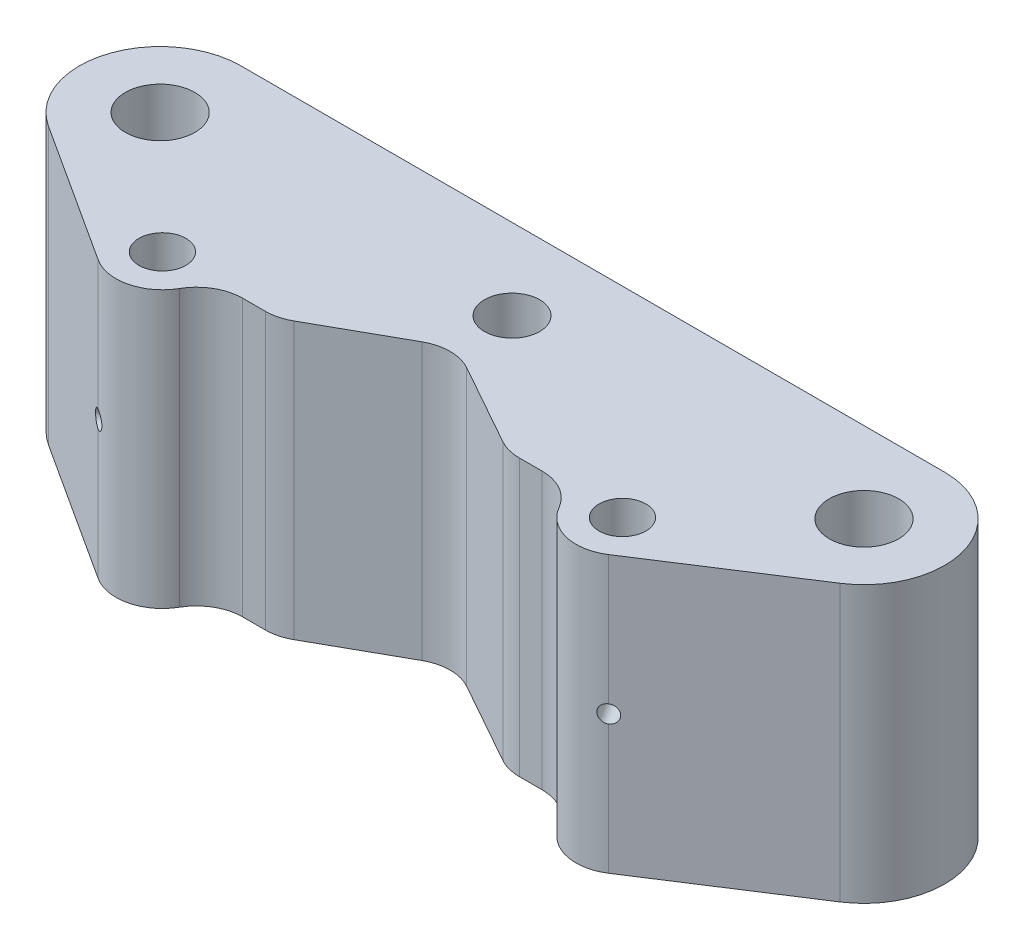
SolidWorks part; units mm, degrees
ref_plane "Płaszczyzna przednia" through (0, 0, 0) normal (0, 0, 1) x (1, 0, 0)
ref_plane "Płaszczyzna górna" through (0, 0, 0) normal (0, 1, 0) x (1, 0, 0)
ref_plane "Płaszczyzna prawa" through (0, 0, 0) normal (1, 0, 0) x (0, 0, -1)
sketch "Szkic1" plane through (0, 0, 0) normal (0, 1, 0) x (1, 0, 0)
  line L0 (-76.5, 17.55) -> (76.5, 17.55)
  line L1 (-86.027, -14.739) -> (-55.4828, -34.4823)
  line L2 (55.4828, -34.4823) -> (86.027, -14.739)
  line L3 (-50, -36.1) -> (50, -36.1)
  line L4 (-39.9, -26) -> (39.9, -26)
  circle A0 centre (-76.5, 0) radius 7.55
  circle A1 centre (76.5, 0) radius 7.55
  circle A2 centre (-76.5, 0) radius 17.55
  circle A3 centre (76.5, 0) radius 17.55
  circle A4 centre (0, 0) radius 6
  circle A5 centre (-50, -26) radius 5.1
  circle A6 centre (50, -26) radius 5.1
  circle A7 centre (-50, -26) radius 10.1
  circle A8 centre (50, -26) radius 10.1
  dimension "D1" = 15.1
  dimension "D2" = 15.1
  dimension "D7" = 12
  dimension "D8" = 10.2
  dimension "D9" = 100
  dimension "D3" = 153
  dimension "D4" = 76.5
  dimension "D10" = 50
  dimension "D11" = 26
  dimension "D5" = 10
  dimension "D6" = 10
  dimension "D12" = 5
extrude "Dodanie-wyciągnięcie1" add sketch "Szkic1" along normal blind 60 contours A2 A0 | A8 L2 A3 L0 A2 L1 A7 L3 A4 | A7 A5 | A8 A6 | A3 A1 region at (0, 0, -15.7525) region at (-64.4413, 0, -12.0587) region at (88.5587, 0, -12.0587) region at (-54.6922, 0, 17.38) region at (52.7774, 0, 35.4131)
sketch "Szkic2" plane through (0, 0, 0) normal (0, -1, 0) x (1, 0, 0)
  circle A0 centre (0, 0) radius 11
  dimension "D1" = 22
extrude "Wytnij-wyciągnięcie1" cut sketch "Szkic2" against normal blind 5
sketch "Szkic3" plane through (0, 5, 0) normal (0, -1, 0) x (1, 0, 0)
  line L0 (0, 0) -> (-5.6569, 5.6569) construction
  line L1 (0, 0) -> (0, 9.4855) construction
  circle A0 centre (0, 0) radius 8 construction
  circle A1 centre (-5.6569, 5.6569) radius 1.25
  circle A2 centre (5.6569, 5.6569) radius 1.25
  circle A3 centre (5.6569, -5.6569) radius 1.25
  circle A4 centre (-5.6569, -5.6569) radius 1.25
  point P15 (0, 0)
  dimension "D1" = 16
  dimension "D2" = 2.5
  dimension "D3" = 45
  dimension "D4" = 4
extrude "Wytnij-wyciągnięcie2" cut sketch "Szkic3" against normal blind 10
sketch "Szkic4" plane through (0, 60, 0) normal (0, 1, 0) x (1, 0, 0)
  line L0 (-25, -26) -> (0, -12)
  line L1 (-39.9, -26) -> (39.9, -26) construction
  line L2 (0, -12) -> (25, -26)
  line L3 (25, -26) -> (-25, -26)
  dimension "D1" = 14
  dimension "D2" = 50
extrude "Wytnij-wyciągnięcie3" cut sketch "Szkic4" against normal through all
fillet "Zaokrąglenie1" radius 10 5 edges at (39.9, 30, 26) (-39.9, 30, 26) (25, 30, 26) (0, 30, 12) (-25, 30, 26)
sketch "Szkic5" plane through (-32.0706, 0, 49.6155) normal (-0.5429, 0, 0.8398) x (0.8398, 0, 0.5429)
  line L0 (-22.7773, 60) -> (-32.9773, 60) construction
  line L1 (-22.7773, 60) -> (-32.9773, 60)
  line L2 (-27.8773, 60) -> (-27.8773, 0) construction
  circle A0 centre (-27.8773, 30) radius 1.9
  dimension "D1" = 3.8
extrude "Wytnij-wyciągnięcie4" cut sketch "Szkic5" against normal blind 20 contours A0
mirror "Lustro1" about plane through (0, 0, 0) normal (1, 0, 0) of "Wytnij-wyciągnięcie4"
sketch "Szkic6" plane through (0, 0, 0) normal (0, -1, 0) x (1, 0, 0)
  circle A0 centre (76.5, 0) radius 7.55 construction
  circle A1 centre (-76.5, 0) radius 7.55 construction
  circle A2 centre (76.5, 0) radius 7.55
  circle A3 centre (-76.5, 0) radius 7.55
  circle A4 centre (-76.5, 0) radius 5.55
  circle A5 centre (76.5, 0) radius 5.55
  dimension "D1" = 2
extrude "Dodanie-wyciągnięcie2" add sketch "Szkic6" against normal blind 4
chamfer "Sfazowanie1" distance 3 angle 45 2 edges at (76.5, 4, -5.55) (-76.5, 4, -5.55)
